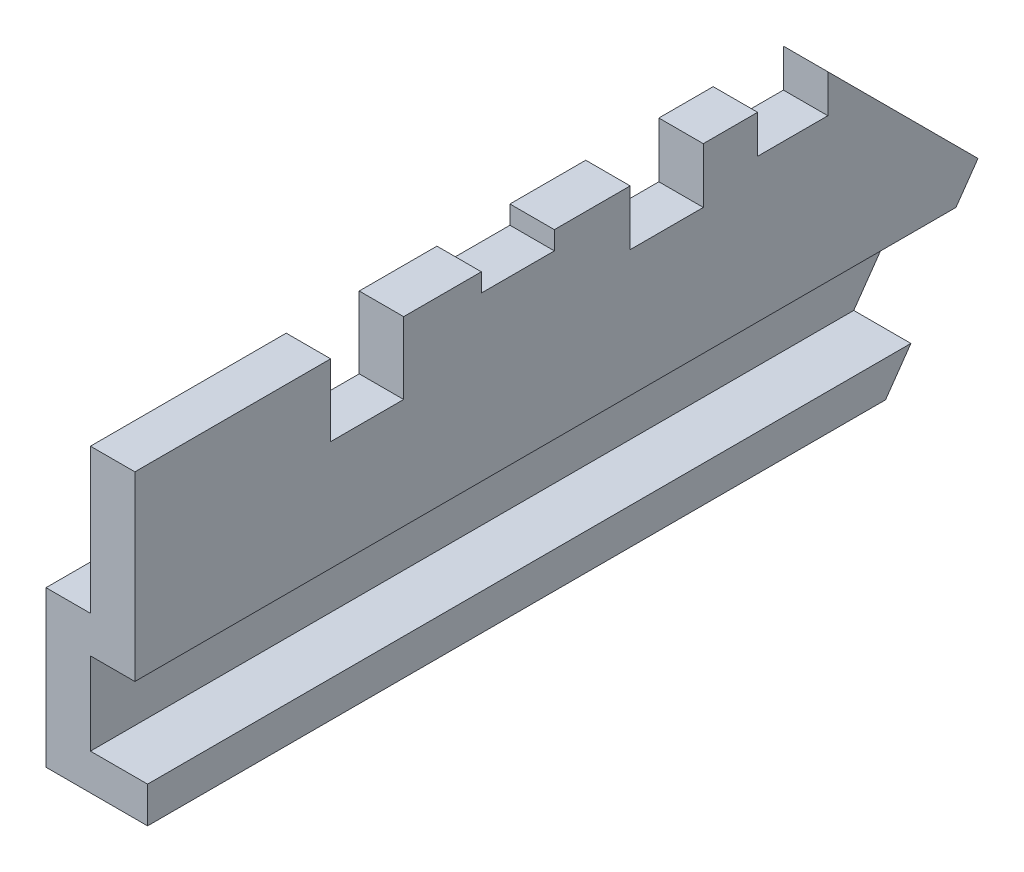
SolidWorks part; units mm, degrees
note: The reader was unsure of these and kept them because the rebuilt part matched: shared geometry of "3DSketch1<3>", "3DSketch1<4>", "3DSketch1<5>".
ref_plane "Front Plane" through (0, 0, 0) normal (0, 0, 1) x (1, 0, 0)
ref_plane "Top Plane" through (0, 0, 0) normal (0, 1, 0) x (1, 0, 0)
ref_plane "Right Plane" through (0, 0, 0) normal (1, 0, 0) x (0, 0, -1)
sketch "Sketch1" plane through (0, 0, 0) normal (0, 0, 1) x (1, 0, 0)
  line L0 (0, 3.8362) -> (0, -3.8362) construction
  line L1 (0, 0) -> (0, 2.28)
  line L2 (0, 2.28) -> (0.7, 2.28)
  line L3 (0.7, 2.28) -> (0.7, -0.58)
  line L4 (0.7, -0.58) -> (0, -0.58)
  line L5 (0, -0.58) -> (0, -1.88)
  line L6 (0.9, -1.88) -> (0, -1.88)
  line L7 (0.9, -1.88) -> (0.9, -2.45)
  line L8 (0.9, -2.45) -> (-0.7, -2.45)
  line L9 (-0.7, -2.45) -> (-0.7, 0)
  line L10 (-0.7, 0) -> (0, 0)
  dimension "D1" = 0.7
  dimension "D2" = 2.86
  dimension "D3" = 1.3
  dimension "D4" = 2.45
  dimension "D5" = 4.73
  dimension "D6" = 1.6
  dimension "D7" = 0.7
extrude "Boss-Extrude1" add sketch "Sketch1" along normal blind 13.28
sketch "Sketch2" plane through (0, 0, 0) normal (1, 0, 0) x (0, 0, -1)
  line L0 (-6.64, 2.28) -> (-6.64, -2.45) construction
  line L1 (-13.28, 2.28) -> (0, 2.28) construction
  line L2 (-13.28, -2.45) -> (0, -2.45) construction
  line L3 (-6.64, -0.085) -> (-13.7893, -0.085) construction
  line L4 (-13.28, -0.085) -> (-10.615, 2.58) construction
  line L5 (-13.28, -0.58) -> (-13.28, 2.28) construction
  line L6 (-10.615, 2.58) -> (-14.08, 2.58) construction
  line L7 (-14.08, 2.58) -> (-14.08, -0.085) construction
  line L8 (-13.28, -0.085) -> (-11.4139, -2.75) construction
  line L9 (-11.4139, -2.75) -> (-14.08, -2.75) construction
  line L10 (-14.08, -2.75) -> (-14.08, -0.085) construction
  line L11 (0.8, -2.75) -> (0.8, -0.085)
  line L12 (-1.8661, -2.75) -> (0.8, -2.75)
  line L13 (0, -0.085) -> (-1.8661, -2.75)
  line L14 (0.8, 2.58) -> (0.8, -0.085)
  line L15 (-2.665, 2.58) -> (0.8, 2.58)
  line L16 (0, -0.085) -> (-2.665, 2.58)
  dimension "D1" = 45
  dimension "D2" = 55
  dimension "D3" = 0.3
  dimension "D4" = 0.3
  dimension "D5" = 0.8
extrude "Cut-Extrude1" cut sketch "Sketch2" against normal through all both and the other way through all
sketch3d "3DSketch1"
  line L0 (0, 2.28, 13.28) -> (0, 2.28, 2.365) construction
  line L1 (0.0493, 2.28, 13.28) -> (0.0493, 2.28, 3.48) construction
  line L2 (0, 2.28, 10.1964) -> (0, 2.28, 9.0464)
  line L3 (0, 2.28, 10.1964) -> (0.7, 2.28, 10.1964)
  line L4 (0.7, 2.28, 10.1964) -> (0.7, 2.28, 9.0464)
  line L5 (0, 2.28, 9.0464) -> (0.7, 2.28, 9.0464)
  line L6 (0.2936, 2.28, 13.28) -> (0.2936, 2.28, 10.25) construction
  line L7 (0.7, 2.28, 13.28) -> (0, 2.28, 13.28) construction
  line L8 (0.5055, 2.28, 13.28) -> (0.5055, 2.28, 7.81) construction
  line L9 (0.1317, 2.28, 13.28) -> (0.1317, 2.28, 5.48) construction
  line L10 (0.7, 2.28, 13.28) -> (0.7, 2.28, 2.365) construction
  line L12 (0.7, 2.28, 7.8225) -> (0.7, 2.28, 6.6725)
  line L13 (0.7, 2.28, 7.8225) -> (0, 2.28, 7.8225)
  line L14 (0, 2.28, 7.8225) -> (0, 2.28, 6.6725)
  line L15 (0.7, 2.28, 6.6725) -> (0, 2.28, 6.6725)
  line L16 (0, 2.28, 5.4786) -> (0, 2.28, 4.3268)
  line L17 (0, 2.28, 5.4786) -> (0.7, 2.28, 5.4786)
  line L18 (0.7, 2.28, 5.4786) -> (0.7, 2.28, 4.3268)
  line L19 (0, 2.28, 4.3268) -> (0.7, 2.28, 4.3268)
  line L20 (0, 2.28, 3.4712) -> (0, 2.28, 2.365)
  line L21 (0, 2.28, 3.4712) -> (0.7, 2.28, 3.4712)
  line L22 (0.7, 2.28, 3.4712) -> (0.7, 2.28, 2.365)
  line L23 (0, 2.28, 2.365) -> (0.7, 2.28, 2.365)
extrude "Cut-Extrude5" cut sketch "3DSketch1" along direction (0, -1, 0) on the side against the normal blind 0.29 contours L13 L14 L15 L12
extrude "Cut-Extrude6" cut sketch "3DSketch1<3>" against normal blind 1.13 contours L2 L5 L4 L3
sketch3d "3DSketch1<3>" same geometry as "3DSketch1"
extrude "Cut-Extrude7" cut sketch "3DSketch1<4>" against normal blind 0.87 contours L19 L18 L17 L16
sketch3d "3DSketch1<4>" same geometry as "3DSketch1"
extrude "Cut-Extrude8" cut sketch "3DSketch1<5>" against normal blind 0.6 contours L20 L23 L22 L21
sketch3d "3DSketch1<5>" same geometry as "3DSketch1"
